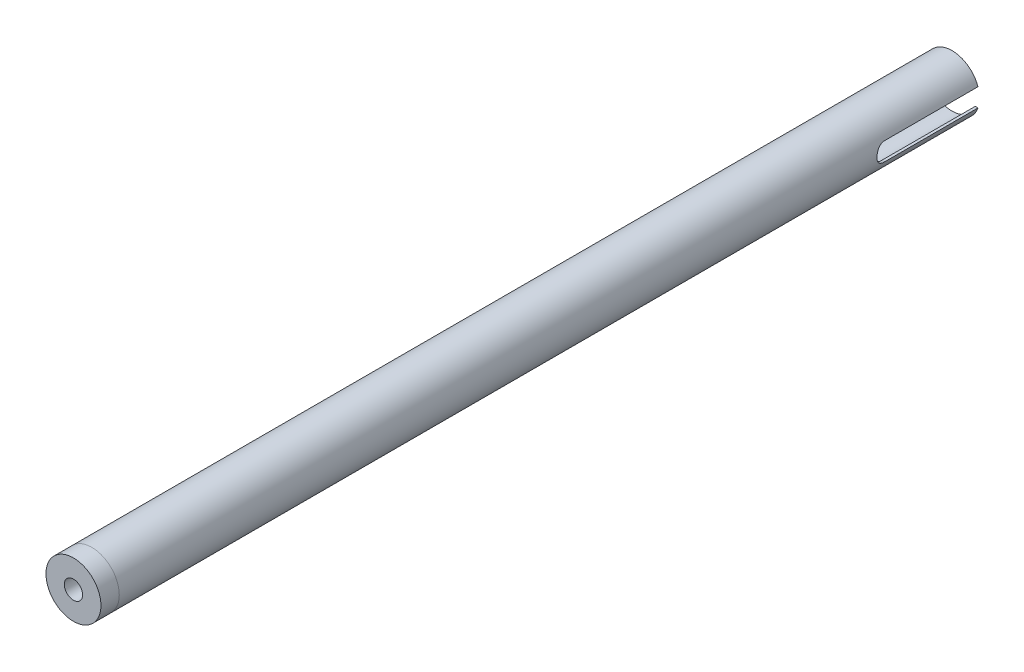
SolidWorks part; units mm, degrees
material "AISI 4130 Steel, normalized at 870C"
ref_plane "Front Plane" through (0, 0, 0) normal (0, 0, 1) x (1, 0, 0)
ref_plane "Top Plane" through (0, 0, 0) normal (0, 1, 0) x (1, 0, 0)
ref_plane "Right Plane" through (0, 0, 0) normal (1, 0, 0) x (0, 0, -1)
sketch "Axis" plane through (0, 0, 0) normal (0, 1, 0) x (1, 0, 0)
  line L0 (0, 0) -> (0, 304.3801) construction
  line L1 (0, 0) -> (0, -21.9075) construction
  line L2 (0, 304.3801) -> (-9.525, 304.3801) construction
  line L5 (0, 332.3201) -> (-22.1542, 267.3343) construction
  point P3 (0, 304.3801)
  point P5 (0, 0)
  point P6 (0, 0)
  point P8 (0, 0)
  point P10 (0, 0)
  dimension "D1" = 21.9075
  dimension "D2" = 9.525
sketch "Sketch1" plane through (0, 0, 0) normal (0, 0, 1) x (1, 0, 0)
  line L0 (-9.525, 0) -> (9.525, 0) construction
  line L1 (-8.9803, 3.175) -> (8.9803, 3.175)
  line L2 (-8.9803, -3.175) -> (8.9803, -3.175)
  circle A0 centre (0, 0) radius 9.525
  circle A1 centre (0, 0) radius 8.636
  circle A2 centre (0, 0) radius 3.175
  dimension "D1" = 19.05
  dimension "D3" = 6.35
  dimension "D2" = 0.889
  dimension "D4" = 6.35
extrude "Threaded insert 1-1" add sketch "Sketch1" against normal blind 6.35 contours A2 L1 A1 | A1 L1 A0 | A2 L0 A1 L1 | A1 L0 A0 L1 | L0 A1 L2 A0 | L0 A2 L2 A1 | A2 L2 A1 | A1 L2 A0 | L0 A1 L2 A2 | L0 A0 L2 A1 | A0 L0 A1 L1 | A1 L0 A2 L1 region at (5.4259, 1.6615, 0) region at (5.4259, -1.6615, 0) region at (8.8881, 1.6046, 0) region at (8.8881, -1.6046, 0) region at (-5.4259, -1.6615, 0) region at (-5.4259, 1.6615, 0) region at (0, 5.4321, 0) region at (0, -5.4321, 0) region at (0, 8.8265, 0) region at (8.5057, -3.3655, 0) region at (-8.8881, -1.6046, 0) region at (-8.8881, 1.6046, 0)
extrude "Threaded insert 1-2" add sketch "Sketch1<3>" against normal blind 6.35 from surface contours A2 L1 A1 | A2 L0 A1 L1 | L0 A2 L2 A1 | A2 L2 A1 | L0 A1 L2 A2 | A1 L0 A2 L1 region at (5.4259, 1.6615, 0) region at (5.4259, -1.6615, 0) region at (-5.4259, -1.6615, 0) region at (-5.4259, 1.6615, 0) region at (0, 5.4321, 0) region at (0, -5.4321, 0) starting at face at (9.525, 0, -6.35)
sketch "Sketch1<3>" plane through (0, 0, 0) normal (0, 0, 1) x (1, 0, 0) same geometry as "Sketch1"
extrude "A-arm tube" add sketch "Sketch1<4>" against normal up to vertex (304.3801 mm away) from surface separate body contours A1 L1 A0 | A1 L0 A0 L1 | L0 A1 L2 A0 | A1 L2 A0 | L0 A0 L2 A1 | A0 L0 A1 L1 region at (8.8881, 1.6046, 0) region at (8.8881, -1.6046, 0) region at (0, 8.8265, 0) region at (8.5057, -3.3655, 0) region at (-8.8881, -1.6046, 0) region at (-8.8881, 1.6046, 0) up to point (0, 0, -304.3801) starting at face at (8.636, 0, -6.35)
sketch "Sketch1<4>" plane through (0, 0, 0) normal (0, 0, 1) x (1, 0, 0) same geometry as "Sketch1"
extrude "Apex slot" cut sketch "Sketch1<5>" along normal blind 35.56 from surface contours A0 L0 A1 L1 | L0 A0 L2 A1 | A1 L0 A0 L1 | L0 A1 L2 A0 region at (8.8881, 1.6046, 0) region at (8.8881, -1.6046, 0) region at (-8.8881, -1.6046, 0) region at (-8.8881, 1.6046, 0) starting at face at (8.636, 0, -304.3801)
sketch "Sketch1<5>" plane through (0, 0, 0) normal (0, 0, 1) x (1, 0, 0) same geometry as "Sketch1"
fillet "Fillet1" radius 3.175 4 edges at (-8.5057, 3.175, -268.8201) (-8.5057, -3.175, -268.8201) (8.5057, -3.175, -268.8201) (8.5057, 3.175, -268.8201)
equation "\"tube diameter\"= 3 / 4"
equation "\"tube thickness\"= .035"
equation "\"apex thickness\"= .25"
equation "\"tube slot\"= 1.4"
equation "\"D1@Sketch1\"=\"tube diameter\""
equation "\"D2@Sketch1\"=\"tube thickness\""
equation "\"threaded insert hole\"= 1 / 4"
equation "\"D3@Sketch1\"=\"threaded insert hole\""
equation "\"D4@Sketch1\"=\"apex thickness\""
equation "\"D1@Apex slot\" = \"tube slot\""
equation "\"D1@Fillet1\"=\"apex thickness\"/2"
equation "\"D2@Axis\"=\"tube diameter\"/2"
